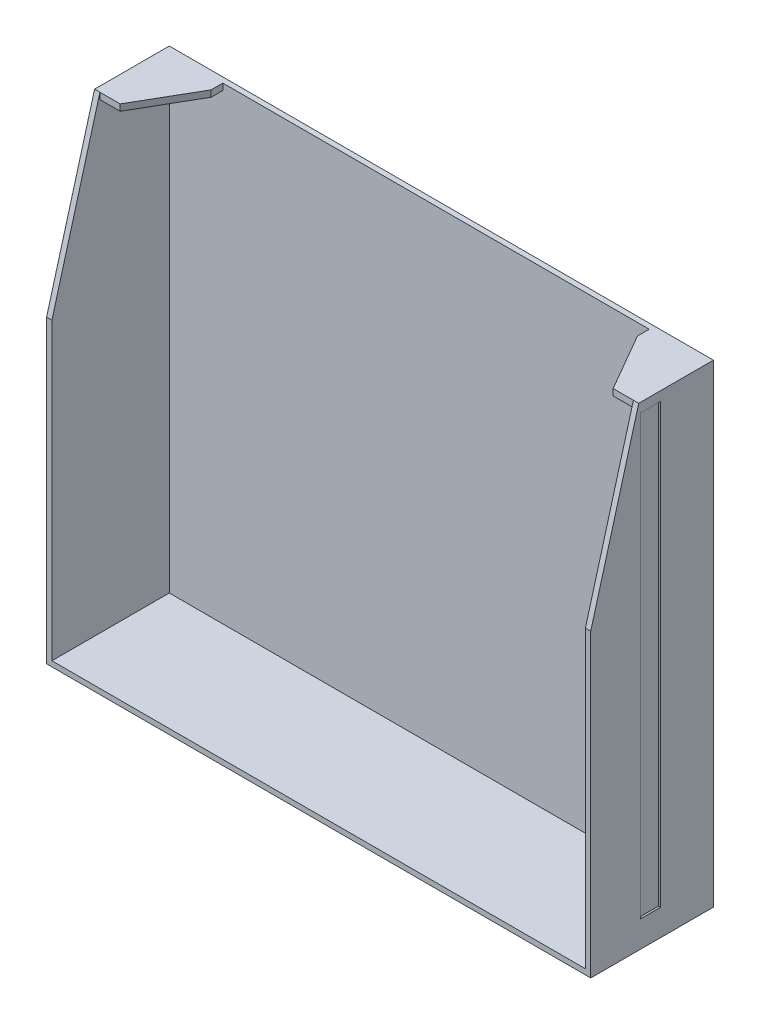
SolidWorks part; units mm, degrees
ref_plane "Front" through (0, 0, 0) normal (0, 0, 1) x (1, 0, 0)
ref_plane "Top" through (0, 0, 0) normal (0, 1, 0) x (1, 0, 0)
ref_plane "Right" through (0, 0, 0) normal (1, 0, 0) x (0, 0, -1)
sketch "Sketch1" plane through (0, 0, 0) normal (0, 0, 1) x (1, 0, 0)
  line L1 (-127.5, -111) -> (127.5, -111)
  line L2 (-127.5, -111) -> (-127.5, 111)
  line L3 (-127.5, 111) -> (127.5, 111)
  line L4 (127.5, -111) -> (127.5, 111)
  line L5 (-127.5, -111) -> (127.5, 111) construction
  line L6 (-127.5, 111) -> (127.5, -111) construction
  point P0 (0, 0)
  dimension "D1" = 222
  dimension "D2" = 255
extrude "Boss-Extrude1" add sketch "Sketch1" against normal blind 2.5
sketch "Sketch2" plane through (0, 0, 0) normal (0, 0, 1) x (1, 0, 0)
  line L0 (-127.5, -111) -> (127.5, -111) construction
  line L1 (-127.5, 111) -> (-125, 111)
  line L2 (-127.5, 111) -> (-127.5, -111)
  line L3 (-127.5, -111) -> (-125, -111)
  line L4 (-125, 111) -> (-125, -111)
  line L6 (127.5, 111) -> (125, 111)
  line L7 (127.5, 111) -> (127.5, -111)
  line L8 (127.5, -111) -> (125, -111)
  line L9 (125, 111) -> (125, -111)
  line L10 (-125, 111) -> (125, 111)
  line L14 (-125, -111) -> (125, -111)
  line L15 (-125, -111) -> (-125, -108.5)
  line L16 (-125, -108.5) -> (125, -108.5)
  line L17 (125, -111) -> (125, -108.5)
  dimension "D1" = 2.5
extrude "Boss-Extrude2" add sketch "Sketch2" along normal blind 55 contours L4 L1 L2 L3 | L16 L4 L14 L9 | L6 L9 L8 L7 region at (-126.25, 0, 0) region at (0, -109.75, 0) region at (126.25, 0, 0)
sketch "Sketch4" plane through (0, 111, 0) normal (0, 1, 0) x (1, 0, 0)
  line L0 (127.5, 2.5) -> (127.5, -32.5)
  line L1 (127.5, 2.5) -> (127.5, -55) construction
  line L2 (127.5, -32.5) -> (115.5, -32.5)
  line L3 (115.5, -32.5) -> (99.9115, -5.5)
  line L4 (99.9115, -5.5) -> (99.9115, 2.5)
  line L5 (127.5, 2.5) -> (-127.5, 2.5) construction
  line L6 (99.9115, 2.5) -> (127.5, 2.5)
  dimension "D1" = 60
  dimension "D2" = 35
  dimension "D3" = 12
  dimension "D4" = 8
extrude "Hold Tab" add sketch "Sketch4" against normal blind 3
mirror "Hold Tabs" about plane through (0, 0, 0) normal (1, 0, 0) of "Hold Tab"
sketch "Sketch5" plane through (0, 0, 0) normal (1, 0, 0) x (0, 0, -1)
  line L0 (-55, 29.728) -> (-32.5, 111)
  line L1 (-55, 111) -> (-55, -111) construction
  line L2 (2.5, 111) -> (-55, 111) construction
  line L3 (-32.5, 111) -> (-55, 111)
  line L4 (-55, 111) -> (-55, 29.728)
extrude "Front Taper" cut sketch "Sketch5" against normal through all both and the other way through all
sketch "Sketch6" plane through (127, 0, 0) normal (-1, 0, 0) x (0, 0, 1)
  line L4 (31.2, -98.2) -> (31.2, 106.2)
  line L5 (31.2, 106.2) -> (22.8, 106.2)
  line L6 (22.8, 106.2) -> (22.8, -98.2)
  line L7 (22.8, -98.2) -> (31.2, -98.2)
  line L8 (31.2, -98.2) -> (31.2, 106.2)
  line L9 (31.2, 106.2) -> (22.8, 106.2)
  line L10 (22.8, 106.2) -> (22.8, -98.2)
  line L11 (22.8, -98.2) -> (31.2, -98.2)
  dimension "D1" = 0
extrude "Mounting Pocket" cut sketch "Sketch6" against normal through all
chamfer "Print Chamfers" distance 0.5 angle 45 4 edges at (127.5, 106.2, 27) (127.5, 4, 22.8) (127.5, -98.2, 27) (127.5, 4, 31.2)
mirror "Mounting Pockets" about plane through (0, 0, 0) normal (1, 0, 0) of "Print Chamfers", "Mounting Pocket"
